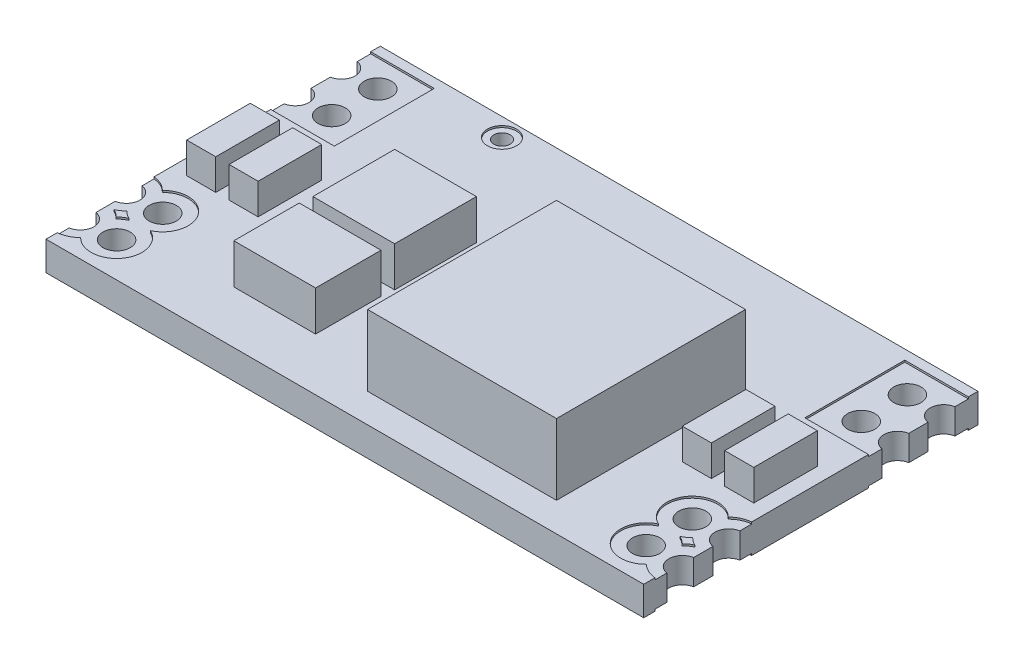
SolidWorks part; units mm, degrees
ref_plane "Front Plane" through (0, 0, 0) normal (0, 0, 1) x (1, 0, 0)
ref_plane "Top Plane" through (0, 0, 0) normal (0, 1, 0) x (1, 0, 0)
ref_plane "Right Plane" through (0, 0, 0) normal (1, 0, 0) x (0, 0, -1)
sketch "Sketch1" plane through (0, 0, 0) normal (0, 1, 0) x (1, 0, 0)
  line L1 (-16.45, 9.2) -> (16.45, 9.2)
  line L2 (-16.45, 9.2) -> (-16.45, -9.2)
  line L3 (-16.45, -9.2) -> (16.45, -9.2)
  line L4 (16.45, 9.2) -> (16.45, -9.2)
  point P4 (0, 9.2)
  point P6 (-16.45, 0)
  dimension "D1" = 32.9
  dimension "D2" = 18.4
extrude "Boss-Extrude1" add sketch "Sketch1" along normal blind 1.6
sketch "Sketch2" plane through (0, 0, 0) normal (0, 1, 0) x (1, 0, 0)
  line L1 (0, -0.88) -> (0, 0.88) construction
  line L2 (-0.88, 0) -> (0.88, 0) construction
  line L3 (-16.45, 9.2) -> (-16.45, -9.2) construction
  line L4 (16.45, 9.2) -> (-16.45, 9.2) construction
  circle A0 centre (-16.575, 7.19) radius 0.75
  circle A1 centre (-16.575, 4.65) radius 0.75
  circle A2 centre (-14.575, 7.19) radius 0.75
  circle A3 centre (-14.575, 4.65) radius 0.75
  circle A4 centre (14.575, 4.65) radius 0.75
  circle A5 centre (14.575, 7.19) radius 0.75
  circle A6 centre (16.575, 4.65) radius 0.75
  circle A7 centre (16.575, 7.19) radius 0.75
  circle A8 centre (16.575, -7.19) radius 0.75
  circle A9 centre (16.575, -4.65) radius 0.75
  circle A10 centre (14.575, -7.19) radius 0.75
  circle A11 centre (14.575, -4.65) radius 0.75
  circle A12 centre (-14.575, -4.65) radius 0.75
  circle A13 centre (-14.575, -7.19) radius 0.75
  circle A14 centre (-16.575, -4.65) radius 0.75
  circle A15 centre (-16.575, -7.19) radius 0.75
  circle A16 centre (-8.75, 8.2) radius 0.45
  dimension "D1" = 1.5
  dimension "D7" = 0.9
  dimension "D2" = 2.54
  dimension "D3" = 29.15
  dimension "D4" = 9.3
  dimension "D5" = 2
  dimension "D6" = 7.7
  dimension "D8" = 1
extrude "Cut-Extrude4" cut sketch "Sketch2" along normal through all
sketch "Sketch4" plane through (0, 1.6, 0) normal (0, 1, 0) x (1, 0, 0)
  line L1 (-16.45, 8.67) -> (-12.95, 8.67)
  line L2 (-16.45, 8.67) -> (-16.45, 3.17)
  line L3 (-16.45, 3.17) -> (-12.95, 3.17)
  line L4 (-12.95, 8.67) -> (-12.95, 3.17)
  line L5 (-14.575, 7.19) -> (-14.575, 4.65) construction
  line L6 (-14.575, 5.92) -> (-12.95, 5.92) construction
  line L7 (-16.45, 9.2) -> (-16.45, 7.9295) construction
  line L8 (0, -0.88) -> (0, 0.88) construction
  line L9 (16.45, 3.17) -> (12.95, 3.17)
  line L10 (12.95, 8.67) -> (12.95, 3.17)
  line L11 (16.45, 8.67) -> (12.95, 8.67)
  line L12 (16.45, 8.67) -> (16.45, 3.17)
  arc A0 (-15.575, -3.6702) -> (-17.1642, -5.92) centre (-16.575, -4.65) ccw
  arc A1 (-15.575, -5.6298) -> (-15.1642, -5.92) centre (-14.575, -4.65) ccw
  arc A2 (-15.575, -6.2102) -> (-15.9858, -5.92) centre (-16.575, -7.19) ccw
  arc A3 (-15.1642, -5.92) -> (-15.575, -6.2102) centre (-14.575, -7.19) ccw
  arc A4 (-13.9858, -5.92) -> (-15.575, -3.6702) centre (-14.575, -4.65) ccw
  arc A5 (-15.575, -8.1698) -> (-13.9858, -5.92) centre (-14.575, -7.19) ccw
  arc A6 (-15.9858, -5.92) -> (-15.575, -5.6298) centre (-16.575, -4.65) ccw
  arc A7 (-17.1642, -5.92) -> (-15.575, -8.1698) centre (-16.575, -7.19) ccw
  arc A8 (15.9858, -5.92) -> (15.575, -5.6298) centre (16.575, -4.65) cw
  arc A9 (15.575, -6.2102) -> (15.9858, -5.92) centre (16.575, -7.19) cw
  arc A10 (15.1642, -5.92) -> (15.575, -6.2102) centre (14.575, -7.19) cw
  arc A11 (15.575, -5.6298) -> (15.1642, -5.92) centre (14.575, -4.65) cw
  arc A12 (13.9858, -5.92) -> (15.575, -3.6702) centre (14.575, -4.65) cw
  arc A13 (15.575, -8.1698) -> (13.9858, -5.92) centre (14.575, -7.19) cw
  arc A14 (17.1642, -5.92) -> (15.575, -8.1698) centre (16.575, -7.19) cw
  arc A15 (15.575, -3.6702) -> (17.1642, -5.92) centre (16.575, -4.65) cw
  circle A16 centre (-8.75, 8.2) radius 0.8
  dimension "D3" = 2.8
  dimension "D4" = 1.6
  dimension "D1" = 5.5
  dimension "D2" = 3.5
extrude "Cut-Extrude5" cut sketch "Sketch4" against normal blind 0.1
ref_plane "Plane1" through (0, 0.8, 0) normal (0, 1, 0) x (1, 0, 0)
mirror "Mirror1" about plane through (0, 0.8, 0) normal (0, 1, 0) of "Cut-Extrude5"
sketch "Sketch3" plane through (0, 1.6, 0) normal (0, 1, 0) x (1, 0, 0)
  line L0 (-16.45, -9.2) -> (16.45, -9.2) construction
  line L1 (-0.35, 2.8) -> (10.05, 2.8)
  line L2 (-0.35, 2.8) -> (-0.35, -7.6)
  line L3 (-0.35, -7.6) -> (10.05, -7.6)
  line L4 (10.05, 2.8) -> (10.05, -7.6)
  line L5 (16.45, -3.9105) -> (16.45, 5.3895) construction
  line L6 (0, -0.88) -> (0, 0.88) construction
  line L7 (13.2749, 1.2) -> (11.6749, 1.2)
  line L8 (13.2749, 1.2) -> (13.2749, -2.3)
  line L9 (13.2749, -2.3) -> (11.6749, -2.3)
  line L10 (11.6749, 1.2) -> (11.6749, -2.3)
  line L11 (15.6069, 1.2) -> (14.0069, 1.2)
  line L12 (15.6069, 1.2) -> (15.6069, -2.3)
  line L13 (15.6069, -2.3) -> (14.0069, -2.3)
  line L14 (14.0069, 1.2) -> (14.0069, -2.3)
  line L15 (-8.9367, 2.4766) -> (-4.4367, 2.4766)
  line L16 (-8.9367, 2.4766) -> (-8.9367, -2.0234)
  line L17 (-8.9367, -2.0234) -> (-4.4367, -2.0234)
  line L18 (-4.4367, 2.4766) -> (-4.4367, -2.0234)
  line L19 (-9.0042, -2.7063) -> (-4.5042, -2.7063)
  line L20 (-9.0042, -2.7063) -> (-9.0042, -6.3063)
  line L21 (-9.0042, -6.3063) -> (-4.5042, -6.3063)
  line L22 (-4.5042, -2.7063) -> (-4.5042, -6.3063)
  line L23 (-15.6069, -2.3) -> (-14.0069, -2.3)
  line L24 (-15.6069, 1.2) -> (-15.6069, -2.3)
  line L25 (-15.6069, 1.2) -> (-14.0069, 1.2)
  line L26 (-14.0069, 1.2) -> (-14.0069, -2.3)
  line L27 (-13.2749, 1.2) -> (-11.6749, 1.2)
  line L28 (-11.6749, 1.2) -> (-11.6749, -2.3)
  line L29 (-13.2749, -2.3) -> (-11.6749, -2.3)
  line L30 (-13.2749, 1.2) -> (-13.2749, -2.3)
  point P34 (-4.5042, -2.0234)
  point P35 (-8.9367, 2.4955)
  dimension "D1" = 10.4
  dimension "D2" = 1.6
  dimension "D3" = 6.4
  dimension "D4" = 3.5
  dimension "D5" = 1.6
  dimension "D6" = 6.9
  dimension "D7" = 3.6
  dimension "D8" = 4.5
extrude "Boss-Extrude2" add sketch "Sketch3" along normal blind 3.9 separate body contours L4 L1 L2 L3 region at (4.85, 1.6, 2.4)
extrude "Boss-Extrude3" add sketch "Sketch3<3>" along normal blind 2.2 contours L22 L19 L20 L21 | L18 L15 L16 L17 region at (-6.6867, 1.6, -0.2266) region at (-6.7542, 1.6, 4.5063)
sketch "Sketch3<3>" plane through (0, 1.6, 0) normal (0, 1, 0) x (1, 0, 0) same geometry as "Sketch3"
extrude "Boss-Extrude4" add sketch "Sketch3<4>" along normal blind 1.7 contours L26 L25 L24 L23 | L27 L30 L29 L28 | L7 L10 L9 L8 | L11 L14 L13 L12 region at (12.4749, 1.6, 0.55) region at (14.8069, 1.6, 0.55) region at (-14.8069, 1.6, 0.55) region at (-12.4749, 1.6, 0.55)
sketch "Sketch3<4>" plane through (0, 1.6, 0) normal (0, 1, 0) x (1, 0, 0) same geometry as "Sketch3"
